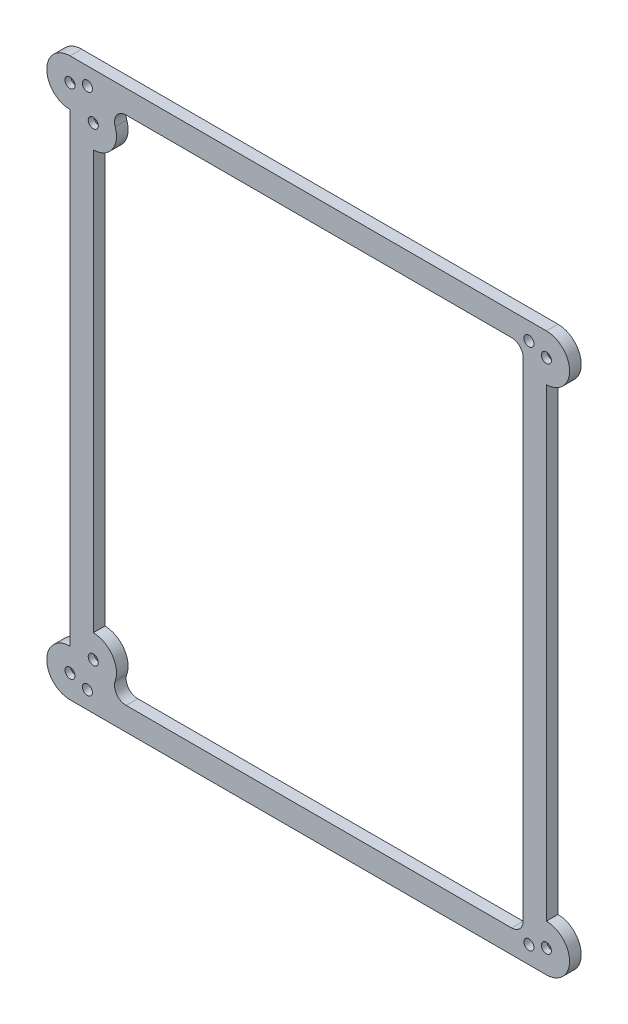
SolidWorks part; units mm, degrees
ref_plane "Front Plane" through (0, 0, 0) normal (0, 0, 1) x (1, 0, 0)
ref_plane "Top Plane" through (0, 0, 0) normal (0, 1, 0) x (1, 0, 0)
ref_plane "Right Plane" through (0, 0, 0) normal (1, 0, 0) x (0, 0, -1)
sketch "Sketch1" plane through (0, 0, 0) normal (0, 0, 1) x (1, 0, 0)
  line L0 (254, 6.35) -> (254, -273.05) construction
  line L1 (-19.05, -285.75) -> (241.3, -285.75)
  line L2 (-19.05, -285.75) -> (-19.05, 19.05)
  line L3 (-19.05, 19.05) -> (241.3, 19.05)
  line L4 (241.3, -285.75) -> (241.3, 19.05)
  line L5 (-19.05, -285.75) -> (241.3, 19.05) construction
  line L6 (-19.05, 19.05) -> (241.3, -285.75) construction
  line L7 (-6.35, 6.35) -> (228.6, 6.35)
  line L8 (-6.35, 6.35) -> (-6.35, -273.05)
  line L9 (-6.35, -273.05) -> (228.6, -273.05)
  line L10 (228.6, 6.35) -> (228.6, -273.05)
  line L11 (-6.35, 6.35) -> (228.6, -273.05) construction
  line L12 (-6.35, -273.05) -> (228.6, 6.35) construction
  circle A0 centre (-9.525, -276.225) radius 2.75
  circle A1 centre (231.775, -276.225) radius 2.75
  circle A2 centre (231.775, 9.525) radius 2.75
  circle A3 centre (-9.525, 9.525) radius 2.75
  circle A4 centre (231.775, 9.525) radius 2.75 construction
  arc A5 (241.3, 19.05) -> (241.3, -6.35) centre (241.3, 6.35) cw
  arc A6 (241.3, -260.35) -> (241.3, -285.75) centre (241.3, -273.05) cw
  arc A7 (-19.05, 19.05) -> (-19.05, -6.35) centre (-19.05, 6.35) ccw
  arc A8 (-19.05, -285.75) -> (-19.05, -260.35) centre (-19.05, -273.05) cw
  circle A9 centre (-19.05, -273.05) radius 2.75
  circle A10 centre (241.3, -273.05) radius 2.75
  circle A11 centre (241.3, 6.35) radius 2.75
  circle A12 centre (-19.05, 6.35) radius 2.75
  circle A13 centre (-6.35, -260.35) radius 2.75
  circle A14 centre (-6.35, -260.35) radius 12.7
  circle A15 centre (-6.35, -6.35) radius 12.7
  circle A16 centre (-6.35, -6.35) radius 2.75
  point P4 (111.125, -133.35)
  point P24 (111.125, -133.35)
  dimension "D1" = 12.7
  dimension "D2" = 12.7
  dimension "D3" = 12.7
extrude "Boss-Extrude1" add sketch "Sketch1" along normal blind 6.35 contours L1 L4 L3 L2 A3 A2 A1 A0 L7 L10 L9 L8 | A6 L4 | A5 L4 | A9 L2 A8 | A12 L2 A7 | A15 L2 A14 L8 | A16 L8 A15 | A16 L8 A15 | L8 A14 A13 | L8 A14 A13
fillet "Fillet1" radius 6.35 4 edges at (228.6, 6.35, 3.175) (228.6, -273.05, 3.175) (-6.35, -273.05, 3.175) (-6.35, 6.35, 3.175)
chamfer "Chamfer1" distance 3.175 angle 45 6 edges at (-16.3, 6.35, 0) (244.05, 6.35, 0) (244.05, -273.05, 0) (-16.3, -273.05, 0) (-3.6, -6.35, 0) (-3.6, -260.35, 0)
